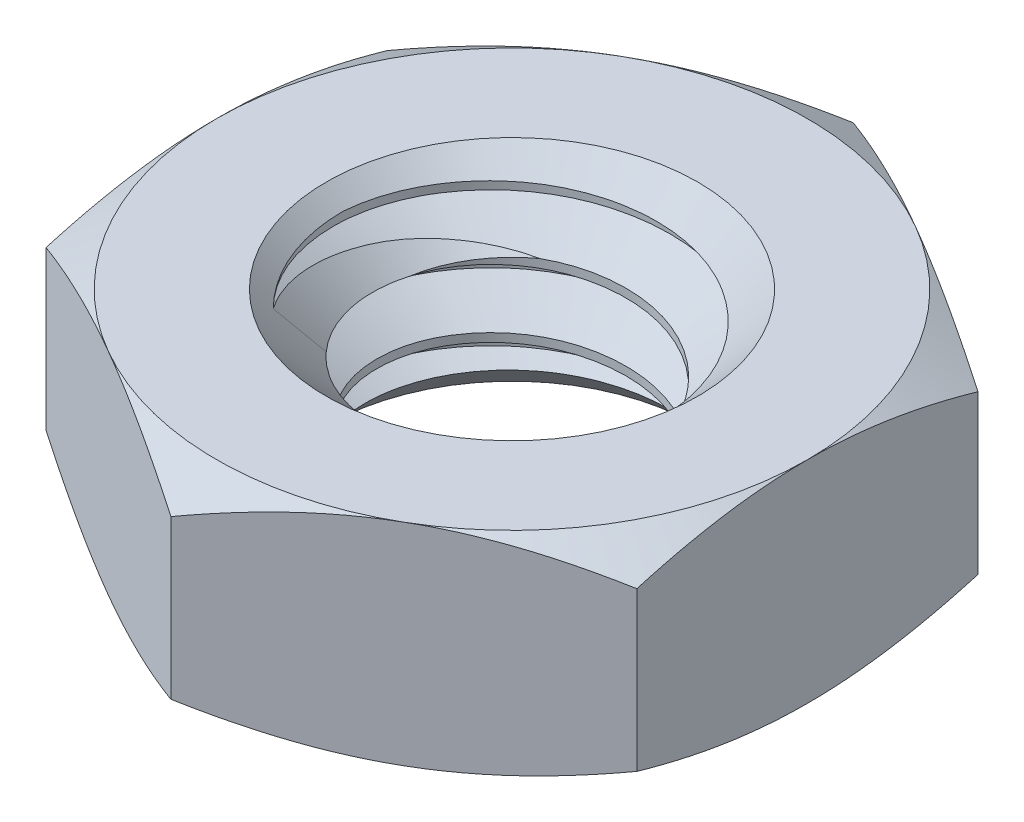
SolidWorks part; units mm, degrees
ref_plane "Front Plane" through (0, 0, 0) normal (0, 0, 1) x (1, 0, 0)
ref_plane "Top Plane" through (0, 0, 0) normal (0, 1, 0) x (1, 0, 0)
ref_plane "Right Plane" through (0, 0, 0) normal (1, 0, 0) x (0, 0, -1)
sketch "Sketch1" plane through (0, 0, 0) normal (0, 0, 1) x (1, 0, 0)
  line L0 (0, -1.9844) -> (0, 1.9844) construction
  line L1 (3.175, 1.9844) -> (-3.175, 1.9844) construction
  line L2 (-5.5562, -1.9844) -> (5.5562, -1.9844) construction
  line L3 (3.175, 1.9844) -> (3.175, 0.7144) construction
  point P4 (0, 0)
  point P8 (0, 1.9844)
  point P10 (0, -1.9844)
  dimension "Height" = 3.9688
  dimension "Width" = 11.1125
  dimension "Thread Dia" = 6.35
  dimension "Pitch" = 1.27
sketch "Sketch2" plane through (0, 0, 0) normal (0, 1, 0) x (1, 0, 0)
  line L1 (0, 6.4158) -> (-5.5562, 3.2079)
  line L2 (-5.5562, 3.2079) -> (-5.5562, -3.2079)
  line L3 (-5.5562, -3.2079) -> (0, -6.4158)
  line L4 (0, -6.4158) -> (5.5562, -3.2079)
  line L5 (5.5562, -3.2079) -> (5.5562, 3.2079)
  line L6 (5.5562, 3.2079) -> (0, 6.4158)
  circle A0 centre (0, 0) radius 5.5562 construction
  circle A1 centre (0, 0) radius 3.175
  point P11 (0, -3.175)
  point P14 (0, 0)
extrude "Boss-Extrude1" add sketch "Sketch2" along normal up to vertex (1.9844 mm away) and the other way up to vertex (1.9844 mm away) up to point (0, 1.9844, 0) other way up to point (0, -1.9844, 0)
sketch "Sketch3" plane through (0, 0, 0) normal (1, 0, 0) x (0, 0, -1)
  line L0 (-6.4158, 1.4881) -> (-5.5562, 1.9844)
  line L1 (-6.4158, 1.9844) -> (-6.4158, -1.9844) construction
  line L2 (-6.4158, 1.9844) -> (-3.2079, 1.9844) construction
  line L3 (-6.4158, -1.4881) -> (-5.5562, -1.9844)
  line L4 (-6.4158, -1.9844) -> (-3.2079, -1.9844) construction
  line L5 (-6.4158, 1.4881) -> (-6.4158, 1.9844)
  line L6 (-6.4158, 1.9844) -> (-5.5562, 1.9844)
  line L7 (-6.4158, -1.4881) -> (-6.4158, -1.9844)
  line L8 (-6.4158, -1.9844) -> (-5.5562, -1.9844)
  line L9 (-5.5562, 1.9844) -> (-5.5562, -1.9844) construction
  line L10 (-3.4925, 1.9844) -> (-3.175, 1.9844)
  line L11 (-3.2079, 1.9844) -> (3.2079, 1.9844) construction
  line L12 (-3.175, 1.9844) -> (-3.175, 1.6669)
  line L13 (-3.175, 1.6669) -> (-3.4925, 1.9844)
  line L14 (-3.4925, -1.9844) -> (-3.175, -1.9844)
  line L15 (-3.2079, -1.9844) -> (3.2079, -1.9844) construction
  line L16 (-3.175, -1.9844) -> (-3.175, -1.6669)
  line L17 (-3.4925, -1.9844) -> (-3.175, -1.6669)
  line L18 (-3.175, 1.6669) -> (-3.175, -1.6669) construction
  line L19 (3.175, 0) -> (-3.175, 0) construction
  line L22 (0, 1.9844) -> (0, -1.9844) construction
  point P15 (-5.5562, 0)
  point P24 (-3.175, 0)
  dimension "D1" = 30
  dimension "D2" = 3.4925
revolve "Cut-Revolve1" cut sketch "Sketch3" angle 360 about L22
sketch "Sketch4" plane through (0, 1.9844, 0) normal (0, 1, 0) x (1, 0, 0)
  circle A0 centre (0, 0) radius 3.175 construction
  circle A1 centre (0, 0) radius 3.175
extrude "Boss-Extrude2" add sketch "Sketch4" against normal up to surface (3.9688 mm away) separate body up to face at (0, -1.9844, 3.4925)
sketch "Sketch5" plane through (0, 1.9844, 0) normal (0, 1, 0) x (1, 0, 0)
  circle A0 centre (0, 0) radius 3.175 construction
  circle A1 centre (0, 0) radius 3.175
curve "Helix/Spiral1" pitch 1.27 height 5.2387 radius 3.175 centre (0, 1.9844, 0) axis (0, -1, 0) start towards (0, 0, 1)
sketch "Sketch6" plane through (0, 0, 0) normal (1, 0, 0) x (0, 0, -1)
  line L0 (-3.3125, 1.905) -> (-2.2126, 2.54) construction
  line L1 (-2.2126, 2.54) -> (-3.3125, 3.175) construction
  line L2 (-3.3125, 3.175) -> (-3.3125, 1.905) construction
  line L3 (-2.3501, 2.6194) -> (-2.3501, 2.4606) construction
  line L4 (-3.175, 3.0956) -> (-3.175, 1.9844) construction
  line L5 (-3.3125, 2.54) -> (-3.175, 2.54) construction
  line L6 (-2.3501, 2.54) -> (-2.2126, 2.54) construction
  line L7 (-3.2437, 2.54) -> (-3.2437, 1.9447) construction
  line L8 (-3.2437, 1.9447) -> (-3.2437, 3.1353)
  line L9 (-3.2437, 3.1353) -> (-2.3501, 2.6194)
  line L10 (-2.3501, 2.6194) -> (-2.3501, 2.4606)
  line L11 (-2.3501, 2.4606) -> (-3.2437, 1.9447)
  dimension "D1" = 1.27
  dimension "D2" = 0.1588
sweep "Cut-Sweep1" cut profiles "Sketch6" path "Helix/Spiral1" align with end faces yes
sketch "Sketch7" plane through (0, 0, 0) normal (1, 0, 0) x (0, 0, -1)
  line L0 (-3.4925, 1.9844) -> (-1.905, 0.3969)
  line L2 (-3.4925, 1.9844) -> (0, 1.9844)
  line L3 (-3.4925, 1.9844) -> (-3.175, 1.9844) construction
  line L4 (-3.4925, -1.9844) -> (0, -1.9844)
  line L5 (-3.4925, -1.9844) -> (-3.175, -1.9844) construction
  line L6 (-3.4925, -1.9844) -> (-1.905, -0.3969)
  line L7 (-3.4925, -1.9844) -> (-3.175, -1.6669) construction
  line L8 (0, -1.9844) -> (0, 1.9844) construction
  line L9 (0, -1.9844) -> (0, 1.9844) construction
  line L12 (-1.905, 0.3969) -> (0, 0.3969)
  line L13 (0, 0.3969) -> (0, 1.9844)
  line L14 (-3.175, 1.6669) -> (-3.4925, 1.9844) construction
  line L15 (-1.905, -0.3969) -> (0, -0.3969)
  line L16 (0, -0.3969) -> (0, -1.9844)
  dimension "D1" = 1.905
revolve "Revolve1" add sketch "Sketch7" angle 360 about L9
sketch "Sketch8" plane through (0, 1.9844, 0) normal (0, 1, 0) x (1, 0, 0)
  circle A0 centre (0, 0) radius 3.4925 construction
  circle A1 centre (0, 0) radius 3.4925
extrude "Boss-Extrude3" add sketch "Sketch8" against normal up to surface (3.9688 mm away) up to face at (0, -1.9844, 3.4925)
combine bodies "Combine1" operation type subtract main body 109 bodies to subtract 108
equation "\"D2@Sketch3\"=\"Thread Dia@Sketch1\"*.55"
equation "\"D4@Helix/Spiral1\"=\"Pitch@Sketch1\""
equation "\"D3@Helix/Spiral1\"=\"Height@Sketch1\"+\"Pitch@Sketch1\""
equation "\"D1@Sketch6\"=\"Pitch@Sketch1\""
equation "\"D2@Sketch6\"=\"Pitch@Sketch1\"/8"
equation "\"D1@Sketch7\"=\"Thread Dia@Sketch1\"*.3"
